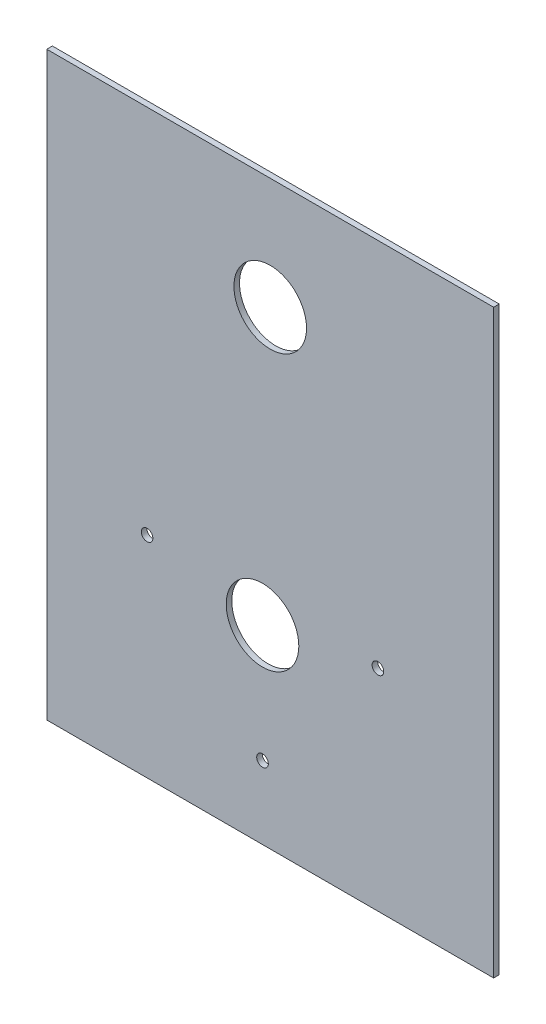
SolidWorks part; units mm, degrees
ref_plane "Front Plane" through (0, 0, 0) normal (0, 0, 1) x (1, 0, 0)
ref_plane "Top Plane" through (0, 0, 0) normal (0, 1, 0) x (1, 0, 0)
ref_plane "Right Plane" through (0, 0, 0) normal (1, 0, 0) x (0, 0, -1)
sketch "Sketch1" plane through (0, 0, 0) normal (0, 0, 1) x (1, 0, 0)
  line L0 (-107.0186, -261.8092) -> (146.9814, -261.8092)
  line L1 (146.9814, -261.8092) -> (146.9814, 68.3908)
  line L2 (146.9814, 68.3908) -> (-107.0186, 68.3908)
  line L3 (-107.0186, 68.3908) -> (-107.0186, -261.8092)
  dimension "D1" = 254
  dimension "D2" = 330.2
extrude "Boss-Extrude1" add sketch "Sketch1" against normal blind 3.175
sketch "Sketch2" plane through (0, 0, 0) normal (0, 0, 1) x (1, 0, 0)
  line L0 (-107.0186, 68.3908) -> (146.9814, 68.3908) construction
  line L1 (146.9814, 68.3908) -> (-107.0186, 68.3908) construction
  line L2 (146.9814, -261.8092) -> (146.9814, 68.3908) construction
  line L3 (19.9814, 68.3908) -> (19.9814, -261.8092) construction
  line L4 (-107.0186, -261.8092) -> (146.9814, -261.8092) construction
  circle A0 centre (19.9814, 4.8908) radius 20.6375
  dimension "D1" = 41.275
  dimension "D2" = 63.5
extrude "Cut-Extrude1" cut sketch "Sketch2" against normal through all
sketch "Sketch3" plane through (0, 0, 0) normal (0, 0, 1) x (1, 0, 0)
  line L0 (-107.0186, 68.3908) -> (-107.0186, -261.8092) construction
  line L1 (-50.0074, -142.2296) -> (15.6054, -153.7989) construction
  line L2 (-107.0186, -261.8092) -> (146.9814, -261.8092) construction
  circle A0 centre (-50.0074, -142.2296) radius 3.3
  circle A1 centre (81.2182, -142.2296) radius 3.3
  circle A2 centre (15.6054, -220.4239) radius 3.3
  circle A3 centre (15.6054, -153.7989) radius 20.6375
  dimension "D1" = 6.6
  dimension "D2" = 6.6
  dimension "D3" = 6.6
  dimension "D4" = 41.275
  dimension "D5" = 122.624
  dimension "D6" = 108.0103
extrude "Cut-Extrude2" cut sketch "Sketch3" against normal through all
